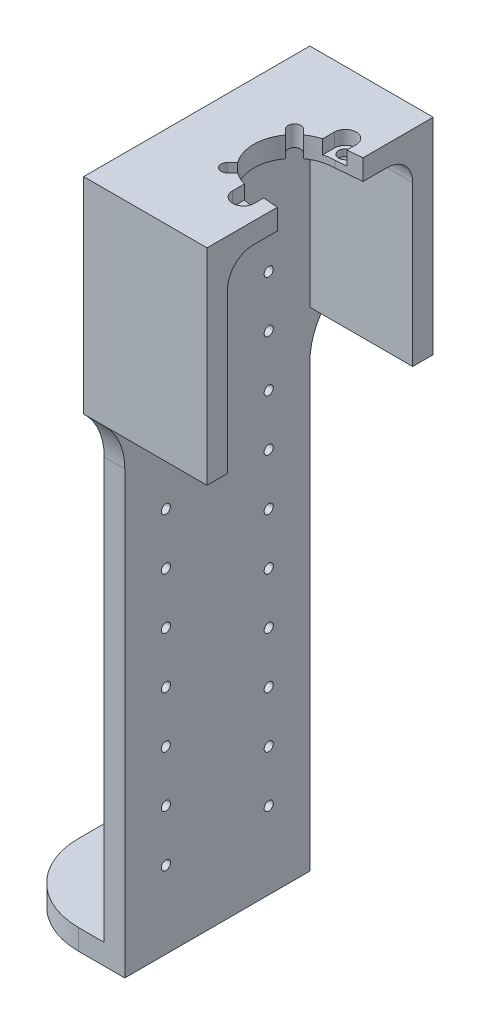
SolidWorks part; units mm, degrees
ref_plane "Front Plane" through (0, 0, 0) normal (0, 0, 1) x (1, 0, 0)
ref_plane "Top Plane" through (0, 0, 0) normal (0, 1, 0) x (1, 0, 0)
ref_plane "Right Plane" through (0, 0, 0) normal (1, 0, 0) x (0, 0, -1)
sketch "Sketch1" plane through (0, 0, 0) normal (0, 0, 1) x (1, 0, 0)
  line L0 (0, 0) -> (0, 131)
  line L1 (0, 131) -> (24, 131)
  line L2 (24, 131) -> (24, 127)
  line L3 (24, 127) -> (4, 127)
  line L4 (4, 127) -> (4, -4)
  line L5 (4, -4) -> (-20, -4)
  line L6 (-20, -4) -> (-20, 0)
  line L7 (-20, 0) -> (0, 0)
  dimension "D1" = 24
  dimension "D2" = 24
  dimension "D3" = 20
  dimension "D4" = 4
  dimension "D5" = 4
  dimension "D6" = 131
  dimension "D7" = 131
extrude "BracketMainBody" add sketch "Sketch1" along normal mid plane 36
sketch "M4_thruHole" plane through (0, -4, 0) normal (0, -1, 0) x (1, 0, 0)
  line L0 (-20, 18) -> (-20, -18) construction
  circle A0 centre (-10, 0) radius 2.4
  dimension "D1" = 4.8
  dimension "D2" = 10
  dimension "D3" = 10
sketch "SQUIDcutouts" plane through (0, 0, 0) normal (0, 1, 0) x (1, 0, 0)
  line L0 (24, -18) -> (24, 18) construction
  line L3 (0, -18) -> (0, 18) construction
  line L4 (24, 0) -> (4, 0) construction
  line L5 (12.6003, 4.6319) -> (11.6161, 5.6161)
  line L6 (13.3839, 7.3839) -> (14.3681, 6.3997)
  line L7 (11.6161, -5.6161) -> (12.6003, -4.6319)
  line L9 (13.3839, -7.3839) -> (14.3681, -6.3997)
  circle A0 centre (19, -9.9) radius 1.3
  circle A1 centre (19, 9.9) radius 1.3
  arc A2 (12.6003, 4.6319) -> (12.6003, -4.6319) centre (19, 0) ccw
  arc A3 (13.3839, 7.3839) -> (11.6161, 5.6161) centre (12.5, 6.5) ccw
  arc A4 (11.6161, -5.6161) -> (13.3839, -7.3839) centre (12.5, -6.5) ccw
  arc A5 (14.3681, -6.3997) -> (14.3681, 6.3997) centre (19, 0) ccw
  dimension "D1" = 5
  dimension "D3" = 2.6
  dimension "D4" = 2.6
  dimension "D9" = 15.8
  dimension "D12" = 2.5
  dimension "D15" = 2.5
  dimension "D18" = 1.3919
  dimension "D2" = 9.9
  dimension "D5" = 5
  dimension "D6" = 9.9
  dimension "D7" = 5
  dimension "D10" = 6.5
  dimension "D11" = 12.5
  dimension "D13" = 6.5
  dimension "D14" = 12.5
  dimension "D16" = 1.3919
  dimension "D17" = 1.3919
  dimension "D19" = 7.9424
extrude "CutExtrude_SQUIDcutouts" cut sketch "SQUIDcutouts" against normal through all from surface contours A0 | A1 | A5 L6 A3 L5 A2 L7 A4 L9 starting at face at (12, 131, 0)
sketch "champhers" plane through (0, 131, 0) normal (0, 1, 0) x (1, 0, 0)
  line L0 (24, 8.3374) -> (24, 6.1164)
  line L1 (24, 6.1164) -> (24, 18) construction
  line L2 (24, 8.3374) -> (19, 7.9)
  line L4 (30.1328, 0) -> (13.0253, 0) construction
  line L5 (24, -6.1164) -> (19, -7.9)
  line L6 (24, -8.3374) -> (19, -7.9)
  line L7 (24, -8.3374) -> (24, -6.1164)
  line L9 (19, 7.9) -> (24, 6.1164)
  arc A0 (14.3681, -6.3997) -> (14.3681, 6.3997) centre (19, 0) ccw construction
  dimension "D2" = 85
extrude "Cut-Extrude7" [suppressed] cut sketch "champhers" against normal through all
sketch "Sketch11" plane through (0, 0, 18) normal (0, 0, 1) x (1, 0, 0)
  line L1 (0, 131) -> (24, 131)
  line L2 (0, 131) -> (0, 91)
  line L3 (0, 91) -> (24, 91)
  line L4 (24, 131) -> (24, 91)
  dimension "D1" = 40
  dimension "D2" = 24
extrude "Extrude_leftWall" add sketch "Sketch11" along normal blind 4
sketch "Sketch12" plane through (0, 0, -18) normal (0, 0, -1) x (-1, 0, 0)
  line L1 (-24, 91) -> (0, 91)
  line L2 (-24, 91) -> (-24, 131)
  line L3 (-24, 131) -> (0, 131)
  line L4 (0, 91) -> (0, 131)
  dimension "D1" = 40
  dimension "D2" = 24
extrude "Extrude_rightWall" add sketch "Sketch12" along normal blind 4
sketch "Sketch13" plane through (0, 131, 0) normal (0, 1, 0) x (1, 0, 0)
  line L0 (19, 9.9) -> (19, -9.9) construction
  line L5 (21.1241, 9.9) -> (21.1241, -9.9)
  line L6 (16.8759, 9.9) -> (16.8759, -9.9)
  arc A3 (21.1241, 9.9) -> (16.8759, 9.9) centre (19, 9.9) ccw
  arc A4 (16.8759, -9.9) -> (21.1241, -9.9) centre (19, -9.9) ccw
  point P3 (19, 0)
  dimension "D1" = 19.8
  dimension "D2" = 2.1241
ref_plane "M2CounterBore_offsetTopPlane" through (0, 128.3, 0) normal (0, 1, 0) x (1, 0, 0)
hole_wizard "M4 Clearance Hole1" positions "3DSketch1" profile "Sketch18" hole size "M4" standard "ANSI Metric" end condition up to next
sketch3d "3DSketch1"
  point P0 (-10, -4, 0)
sketch "Sketch18" plane through (-10, -4, 0) normal (1, 0, 0) x (0, 0, -1)
  line L0 (0, 0) -> (0, 4)
  line L1 (0, 4) -> (2.25, 4)
  line L2 (2.25, 4) -> (2.25, 0)
  line L5 (2.25, 0) -> (0, 0)
  line L11 (0, -6.35) -> (0, 107.95) construction
  dimension "Thru Hole Dia." = 4.5
  dimension "Thru Hole Depth" = 4
extrude "Cut-Extrude12" cut sketch "champhers<2>" against normal up to next
sketch "champhers<2>" plane through (0, 131, 0) normal (0, 1, 0) x (1, 0, 0) same geometry as "champhers"
fillet "Fillet2" radius 5 1 edges at (14, 127, 18)
fillet "Fillet3" radius 5 1 edges at (14, 127, -18)
fillet "Fillet4" radius 12.7 1 edges at (2, 91, -18)
fillet "Fillet5" radius 12.7 1 edges at (2, 91, 18)
fillet "Fillet11" radius 15 1 edges at (-20, -2, -18)
fillet "Fillet12" radius 15 1 edges at (-20, -2, 18)
fillet "Fillet13" [suppressed] radius 7.54
sketch "Sketch24" plane through (0, 0, 0) normal (1, 0, 0) x (0, 0, -1)
  line L0 (0, 0) -> (0, 131) construction
  line L1 (-22, 131) -> (22, 131) construction
  point P0 (10, 121)
  dimension "D1" = 10
  dimension "D2" = 10
hole_wizard "#2-56 Tapped Hole1" positions "3DSketch5" profile "Sketch25" tap size "#2-56" standard "ANSI Inch" end condition up to next
sketch3d "3DSketch5"
  line L0 (0, 0, 0) -> (0, 131, 0) construction
  line L1 (0, 131, 22) -> (0, 131, -22) construction
  point P4 (0, 121, -10)
  dimension "D1" = 10
  dimension "D2" = 10
sketch "Sketch25" plane through (0, 121, -10) normal (0, 1, 0) x (0, 0, 1)
  line L0 (0, 0) -> (0, 4.001)
  line L1 (0, 4.001) -> (0.889, 4.001)
  line L2 (0.889, 4.001) -> (0.889, 0)
  line L5 (0.889, 0) -> (0, 0)
  line L11 (0, -6.35) -> (0, 107.95) construction
  dimension "Thru Tap Drill Dia." = 1.778
  dimension "Thru Tap Drill Depth" = 4.001
cosmetic thread "Hole Thread2" parameters "D2"=2.1844
pattern_linear "LPattern3" count 12 spacing 10 along (0, -1, 0) count 2 spacing 20 along (0, 0, 1) of "#2-56 Tapped Hole1"
cosmetic thread "Hole Thread3" parameters "D2"=2.1844
cosmetic thread "Hole Thread4" parameters "D2"=2.1844
cosmetic thread "Hole Thread5" parameters "D2"=2.1844
cosmetic thread "Hole Thread6" parameters "D2"=2.1844
cosmetic thread "Hole Thread7" parameters "D2"=2.1844
cosmetic thread "Hole Thread8" parameters "D2"=2.1844
cosmetic thread "Hole Thread9" parameters "D2"=2.1844
cosmetic thread "Hole Thread10" parameters "D2"=2.1844
cosmetic thread "Hole Thread11" parameters "D2"=2.1844
cosmetic thread "Hole Thread12" parameters "D2"=2.1844
cosmetic thread "Hole Thread13" parameters "D2"=2.1844
cosmetic thread "Hole Thread14" parameters "D2"=2.1844
cosmetic thread "Hole Thread15" parameters "D2"=2.1844
cosmetic thread "Hole Thread16" parameters "D2"=2.1844
cosmetic thread "Hole Thread17" parameters "D2"=2.1844
cosmetic thread "Hole Thread18" parameters "D2"=2.1844
cosmetic thread "Hole Thread19" parameters "D2"=2.1844
cosmetic thread "Hole Thread20" parameters "D2"=2.1844
cosmetic thread "Hole Thread21" parameters "D2"=2.1844
cosmetic thread "Hole Thread22" parameters "D2"=2.1844
cosmetic thread "Hole Thread23" parameters "D2"=2.1844
cosmetic thread "Hole Thread24" parameters "D2"=2.1844
cosmetic thread "Hole Thread25" parameters "D2"=2.1844
fillet "Fillet15" [suppressed] radius 3.8
fillet "Fillet16" [suppressed] radius 7.54
fillet "Fillet17" [suppressed] radius 7.54
extrude "Cut-Extrude14" cut sketch "Sketch13" against normal up to surface (2.7 mm away) contours L5 A4 L6 A3 up to plane "M2CounterBore_offsetTopPlane"
